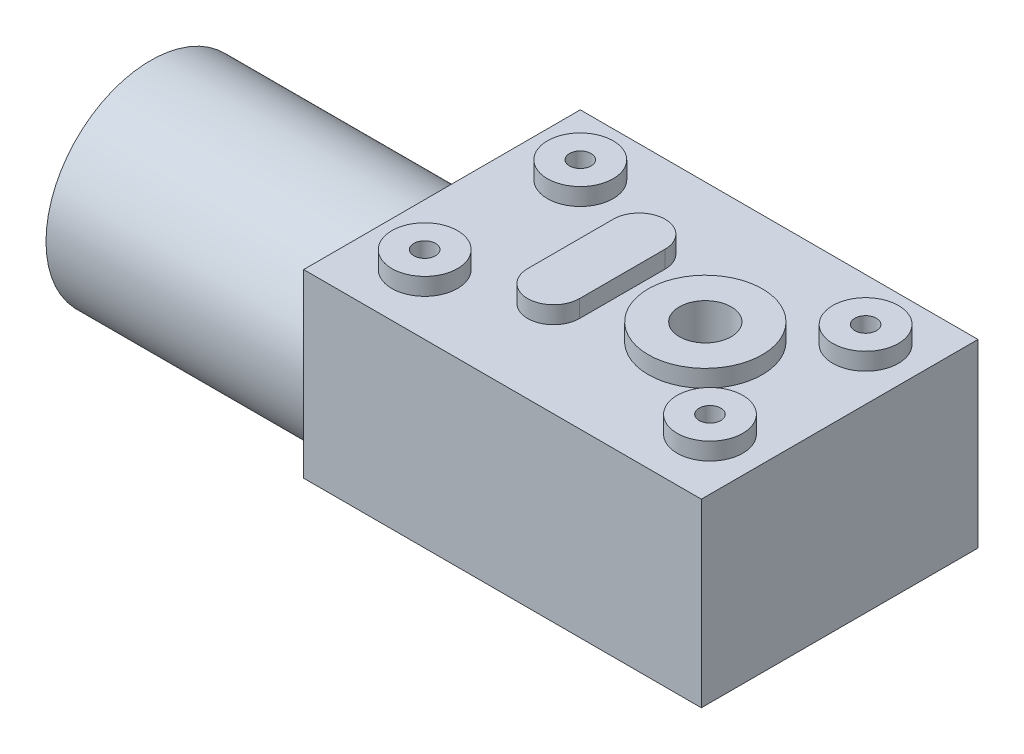
SolidWorks part; units mm, degrees
ref_plane "Front Plane" through (0, 0, 0) normal (0, 0, 1) x (1, 0, 0)
ref_plane "Top Plane" through (0, 0, 0) normal (0, 1, 0) x (1, 0, 0)
ref_plane "Right Plane" through (0, 0, 0) normal (1, 0, 0) x (0, 0, -1)
sketch "Sketch1" plane through (0, 0, 0) normal (0, 1, 0) x (1, 0, 0)
  line L1 (-23, -16) -> (23, -16)
  line L2 (-23, -16) -> (-23, 16)
  line L3 (-23, 16) -> (23, 16)
  line L4 (23, -16) -> (23, 16)
  line L5 (-23, -16) -> (23, 16) construction
  line L6 (-23, 16) -> (23, -16) construction
  line L7 (-16.5394, 9.0215) -> (16.4606, 9.0215)
  line L8 (-16.5394, 9.0215) -> (-16.5394, -8.9785)
  line L9 (-16.5394, -8.9785) -> (16.4606, -8.9785)
  line L10 (16.4606, 9.0215) -> (16.4606, -8.9785)
  circle A0 centre (7.4606, 0) radius 3
  point P1 (0, 0)
  dimension "D3" = 33
  dimension "D8" = 6
  dimension "D1" = 32
  dimension "D2" = 46
  dimension "D4" = 18
  dimension "D5" = 9
extrude "Boss-Extrude1" add sketch "Sketch1" along normal blind 22.3 contours L2 | L1 L4 L3 L2 L7 L10 L9 L8 | L10 L7 L8 L9 A0 region at (-22.4396, 0, 0) region at (-0.4142, 0, -0.0226)
sketch "Sketch3" plane through (0, 22.3, 0) normal (0, 1, 0) x (1, 0, 0)
  line L0 (-23, -16) -> (-23, 16) construction
  line L1 (-16, -9) -> (17, -9) construction
  line L2 (-16, -9) -> (-16, 9) construction
  line L3 (-16, 9) -> (17, 9) construction
  line L4 (17, -9) -> (17, 9) construction
  line L5 (-23, 16) -> (23, 16) construction
  line L6 (-5.1394, -4.95) -> (-5.1394, 4.95) construction
  line L7 (-8.1394, -4.95) -> (-8.1394, 4.95)
  line L8 (-2.1394, -4.95) -> (-2.1394, 4.95)
  line L9 (23, 0) -> (-23, 0) construction
  line L10 (23, -16) -> (23, 16) construction
  line L11 (-2.1394, 0) -> (0.8606, 0) construction
  circle A0 centre (-16, -9) radius 3.8
  circle A1 centre (-16, 9) radius 3.8
  circle A2 centre (17, 9) radius 3.8
  circle A3 centre (17, -9) radius 3.8
  circle A4 centre (7.4606, 0) radius 6.6
  arc A5 (-8.1394, -4.95) -> (-2.1394, -4.95) centre (-5.1394, -4.95) ccw
  arc A6 (-2.1394, 4.95) -> (-8.1394, 4.95) centre (-5.1394, 4.95) ccw
  point P17 (-5.1394, 0)
  dimension "D5" = 7.6
  dimension "D6" = 13.2
  dimension "D1" = 33
  dimension "D2" = 18
  dimension "D3" = 7
  dimension "D4" = 7
  dimension "D7" = 6
  dimension "D8" = 9.9
  dimension "D9" = 3
extrude "Boss-Extrude3" add sketch "Sketch3" along normal blind 2
sketch "Sketch2" plane through (-23, 0, 0) normal (-1, 0, 0) x (0, 0, 1)
  line L0 (2.9, 21.3) -> (2.9, 22.3) construction
  line L1 (16, 22.3) -> (-16, 22.3) construction
  line L2 (15, 9.2) -> (16, 9.2) construction
  line L3 (16, 22.3) -> (16, 0) construction
  circle A0 centre (2.9, 9.2) radius 12.1
  dimension "D1" = 24.2
  dimension "D2" = 1
  dimension "D3" = 1
sketch "Sketch4" plane through (0, 22.3, 0) normal (0, -1, 0) x (1, 0, 0)
  circle A0 centre (7.4606, 0) radius 3 construction
  circle A1 centre (7.4606, 0) radius 3
extrude "Cut-Extrude1" cut sketch "Sketch4" against normal through all
extrude "Boss-Extrude2" add sketch "Sketch2" along normal blind 30.8
chamfer "Chamfer1" distance 1.4 angle 75 3 edges at (0, 0, 16) (23, 0, 0) (0, 0, -16) first distance on face at (0, 11.15, 16) first distance on face at (23, 11.15, 0) first distance on face at (0, 11.15, -16)
hole_wizard "Tap Drill for M3x0.5 Tap1" positions "Sketch5" profile "Sketch6" hole size "M3x0.5" standard "ANSI Metric"
sketch "Sketch5" plane through (0, 24.3, 0) normal (0, 1, 0) x (1, 0, 0)
  point P0 (-16, -9)
  point P5 (17, 9)
  point P8 (17, -9)
  point P11 (-16, 9)
sketch "Sketch6" plane through (-16, 24.3, 9) normal (1, 0, 0) x (0, 0, 1)
  line L0 (0, 0) -> (0, 3.3511)
  line L1 (0, 3.3511) -> (1.25, 2.6)
  line L2 (1.25, 2.6) -> (1.25, 0)
  line L5 (1.25, 0) -> (0, 0)
  line L10 (0, 3.3511) -> (-1.25, 2.6) construction
  line L11 (0, -6.35) -> (0, 107.95) construction
  dimension "Hole Dia." = 2.5
  dimension "Hole Depth" = 2.6
  dimension "Drill Angle" = 118
sketch "Sketch8" plane through (-53.8, 0, 0) normal (-1, 0, 0) x (0, 0, 1)
  circle A3 centre (2.9, 9.2) radius 11.8
  circle A4 centre (2.9, 9.2) radius 11.8
  dimension "D1" = 0.3
extrude "Cut-Extrude2" cut sketch "Sketch8" against normal blind 0.8
sketch "Sketch7" plane through (-53, 0, 0) normal (-1, 0, 0) x (0, 0, 1)
  circle A0 centre (2.9, 9.2) radius 3.2
  dimension "D1" = 6.4
extrude "Boss-Extrude5" add sketch "Sketch7" along normal blind 2.7
